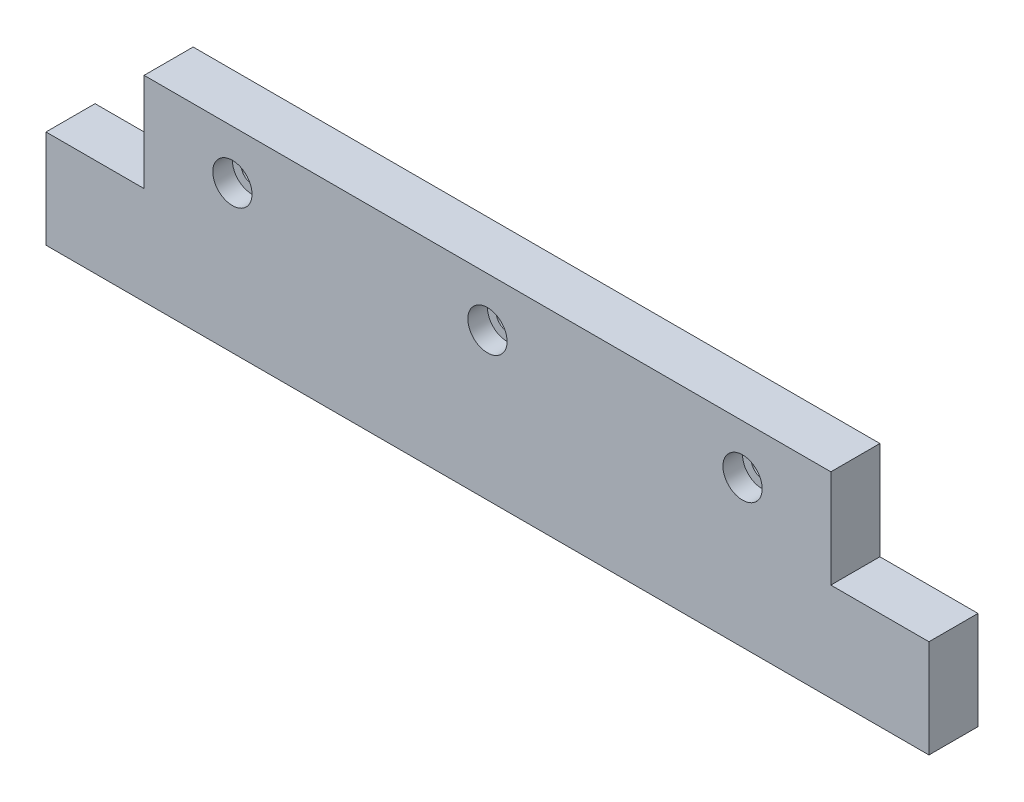
SolidWorks part; units mm, degrees
ref_plane "Płaszczyzna przednia" through (0, 0, 0) normal (0, 0, 1) x (1, 0, 0)
ref_plane "Płaszczyzna górna" through (0, 0, 0) normal (0, 1, 0) x (1, 0, 0)
ref_plane "Płaszczyzna prawa" through (0, 0, 0) normal (1, 0, 0) x (0, 0, -1)
sketch "Szkic1" plane through (0, 0, 0) normal (0, 0, 1) x (1, 0, 0)
  line L0 (0, -20) -> (-20, -20)
  line L2 (0, -20) -> (0, 0)
  line L3 (0, 0) -> (140, 0)
  line L4 (140, -20) -> (140, 0)
  line L7 (-20, -20) -> (-20, -40)
  line L8 (-20, -40) -> (160, -40)
  line L9 (160, -40) -> (160, -20)
  line L10 (160, -20) -> (140, -20)
  point P0 (0, 0)
  point P10 (0, 0)
  dimension "D1" = 180
  dimension "D2" = 40
  dimension "D3" = 20
  dimension "D4" = 20
  dimension "D5" = 20
extrude "Dodanie-wyciągnięcie1" add sketch "Szkic1" along normal blind 10
sketch "Szkic2" plane through (0, 0, 10) normal (0, 0, 1) x (1, 0, 0)
  line L0 (140, 0) -> (0, 0) construction
  line L1 (0, 0) -> (0, -20) construction
  line L2 (140, -20) -> (140, 0) construction
  circle A0 centre (18, -10) radius 2.2
  circle A1 centre (70, -10) radius 2.2
  circle A2 centre (122, -10) radius 2.2
  point P6 (0, 0)
  point P7 (0, 0)
  point P12 (0, 0)
  point P13 (0, 0)
  point P14 (70, 0)
  dimension "D1" = 10
  dimension "D4" = 4.4
  dimension "D2" = 18
  dimension "D3" = 18
extrude "Wytnij-wyciągnięcie1" cut sketch "Szkic2" against normal blind 10
sketch "Szkic3" plane through (0, 0, 10) normal (0, 0, 1) x (1, 0, 0)
  circle A0 centre (122, -10) radius 2.2 construction
  circle A1 centre (70, -10) radius 2.2 construction
  circle A2 centre (18, -10) radius 2.2 construction
  circle A3 centre (122, -10) radius 2.2
  circle A4 centre (70, -10) radius 2.2
  circle A5 centre (18, -10) radius 2.2
  circle A6 centre (18, -10) radius 4
  circle A7 centre (70, -10) radius 4
  circle A8 centre (122, -10) radius 4
  dimension "D1" = 8
  dimension "D2" = 8
  dimension "D3" = 8
extrude "Wytnij-wyciągnięcie2" cut sketch "Szkic3" against normal blind 4
